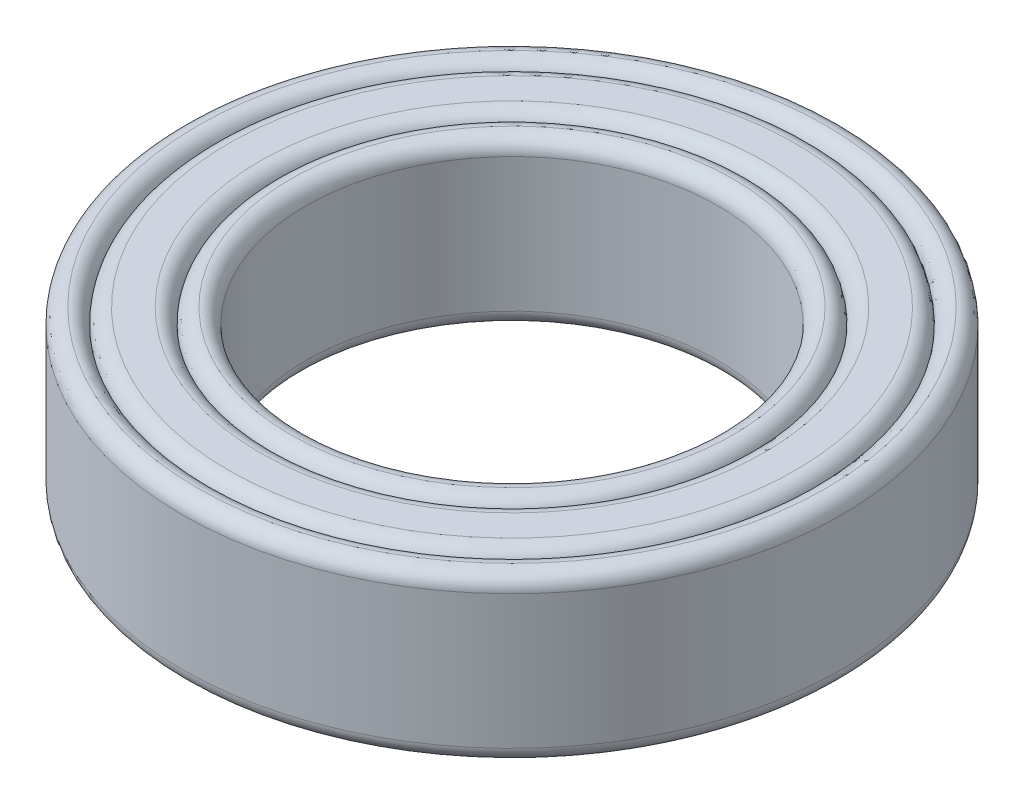
SolidWorks part; units mm, degrees
ref_plane "Front Plane" through (0, 0, 0) normal (0, 0, 1) x (1, 0, 0)
ref_plane "Top Plane" through (0, 0, 0) normal (0, 1, 0) x (1, 0, 0)
ref_plane "Right Plane" through (0, 0, 0) normal (1, 0, 0) x (0, 0, -1)
sketch "Sketch1" plane through (0, 0, 0) normal (0, 1, 0) x (1, 0, 0)
  circle A0 centre (0, 0) radius 8
  dimension "D1" = 16
extrude "Boss-Extrude1" add sketch "Sketch1" along normal mid plane 4
fillet "Fillet1" radius 0.375 2 edges at (0, -2, 8) (0, 2, 8)
sketch "Sketch2" plane through (0, 0, 0) normal (0, 1, 0) x (1, 0, 0)
  circle A0 centre (0, 0) radius 7.25
  dimension "D1" = 14.5
extrude "Cut-Extrude1" cut sketch "Sketch2" against normal through all both and the other way through all
fillet "Fillet2" radius 0.375 2 edges at (0, 2, 7.25) (0, -2, 7.25)
sketch "Sketch3" plane through (0, 0, 0) normal (0, 1, 0) x (1, 0, 0)
  circle A0 centre (0, 0) radius 7.25
  dimension "D1" = 14.5
extrude "Boss-Extrude2" add sketch "Sketch3" along normal through all and the other way through all
fillet "Fillet3" radius 0.375 2 edges at (0, -2, 7.25) (0, 2, 7.25)
sketch "Sketch4" plane through (0, 0, 0) normal (0, 1, 0) x (1, 0, 0)
  circle A0 centre (0, 0) radius 5.75
  dimension "D1" = 11.5
extrude "Cut-Extrude2" cut sketch "Sketch4" against normal through all both and the other way through all
fillet "Fillet4" radius 0.375 2 edges at (0, 2, 5.75) (0, -2, 5.75)
sketch "Sketch5" plane through (0, 0, 0) normal (0, 1, 0) x (1, 0, 0)
  circle A0 centre (0, 0) radius 5.75
  dimension "D1" = 11.5
extrude "Boss-Extrude3" add sketch "Sketch5" along normal through all and the other way through all
fillet "Fillet5" radius 0.375 2 edges at (0, -2, 5.75) (0, 2, 5.75)
sketch "Sketch6" plane through (0, 0, 0) normal (0, 1, 0) x (1, 0, 0)
  circle A0 centre (0, 0) radius 5
  dimension "D1" = 10
extrude "Cut-Extrude3" cut sketch "Sketch6" against normal through all both and the other way through all
fillet "Fillet6" radius 0.375 2 edges at (0, 2, 5) (0, -2, 5)
equation "\"D1@Boss-Extrude1\" = \"ARM Both Nema Bearing Thickness\""
equation "\"D1@Sketch1\" = \"ARM Both Nema Bearing OD\""
equation "\"D1@Fillet1\" = \"ALL Small Fillet\" * ( 3 / 4 )"
equation "\"D1@Fillet2\" = \"ALL Small Fillet\" * ( 3 / 4 )"
equation "\"D1@Fillet3\" = \"ALL Small Fillet\" * ( 3 / 4 )"
equation "\"D1@Fillet4\" = \"ALL Small Fillet\" * ( 3 / 4 )"
equation "\"D1@Fillet5\" = \"ALL Small Fillet\" * ( 3 / 4 )"
equation "\"D1@Fillet6\"= \"ALL Small Fillet\" * ( 3 / 4 )"
equation "\"D1@Sketch2\" = \"ARM Both Nema Bearing OD\" - ( ( \"ARM Both Nema Bearing OD\" - \"ARM Both Nema Bearing ID\" ) / 4 )"
equation "\"D1@Sketch6\" = \"ARM Both Nema Bearing ID\""
equation "\"D1@Sketch4\" = \"ARM Both Nema Bearing ID\" + ( ( \"ARM Both Nema Bearing OD\" - \"ARM Both Nema Bearing ID\" ) / 4 )"
equation "\"D1@Sketch3\" = \"ARM Both Nema Bearing OD\" - ( ( \"ARM Both Nema Bearing OD\" - \"ARM Both Nema Bearing ID\" ) / 4 )"
equation "\"D1@Sketch5\" = \"ARM Both Nema Bearing ID\" + ( ( \"ARM Both Nema Bearing OD\" - \"ARM Both Nema Bearing ID\" ) / 4 )"
equation "\"ALL Big Fillet\"= 10.0mm"
equation "\"ALL Medium Fillet\"= 1.0mm"
equation "\"ALL Small Fillet\"= 0.5mm"
equation "\"BODY Rad\"= 82.5mm"
equation "\"BODY End Cut Rad\"= 72.5mm"
equation "\"BODY Height Ext\"= 27.5mm"
equation "\"BODY Bottom Cut Dist\"= 50.0mm"
equation "\"BODY Seal Thickness\"= 3.75mm"
equation "\"BODY Wall Extra Thickness\"= 2.5mm"
equation "\"BODY Bottom Extra Nut Wall\"= 7.5mm"
equation "\"ARM Both Dia\"= 39.75mm"
equation "\"ARM Both Length\"= 67.5mm"
equation "\"ARM Both Wire Hole Dia\"= 15.0mm"
equation "\"ARM Both Prop Seal Thickness\"= 2.5mm"
equation "\"ARM Both Brass Insert Dia\"= 4.875mm"
equation "\"ARM Both Bolt Cut Depth\"= 12.5mm"
equation "\"ARM Both Nema Bolt Off\"= 15.4mm"
equation "\"ARM Both Nema Bolt Depth\"= 2.5mm"
equation "\"ARM Both Nema Width\"= 20.0mm"
equation "\"ARM Both Nema Wall Off\"= 2.5mm"
equation "\"ARM Both Nema Center Dia 1\"= 17.0mm"
equation "\"ARM Both Nema Center Dia 2\"= 10.0mm"
equation "\"ARM Both Nema Bearing OD\"= 16.0mm"
equation "\"ARM Both Nema Bearing ID\"= 10.0mm"
equation "\"ARM Both Nema Bearing Thickness\"= 4.0mm"
equation "\"ARM Both Nema Height\"= 38.0mm"
equation "\"ARM Both Nema Shaft Dia\"= 4.0mm"
equation "\"ARM Both Nema Shaft Length\"= 10.0mm"
equation "\"ARM Both Nema Center Height\"= 1.5mm"
equation "\"ARM Rotating Bearing OD\"= 68.0mm"
equation "\"ARM Rotating Bearing ID\"= 40.0mm"
equation "\"ARM Rotating Bearing Thickness\"= 15.0mm"
equation "\"ARM Static Mount Dia\"= 65.0mm"
equation "\"ARM Static Bolt Off\"= 1.125mm"
equation "\"ALL Bolt Hole Off\"= 0.25mm"
equation "\"ALL Vert Bolt Hole Off Scalar\"= 0.5mm"
equation "\"ALL Horz Bolt Hole Off Scalar\"= 1.25mm"
equation "\"ALL Nut Size Off\"= 0.25mm"
equation "\"ALL Vert Nut Off Scalar\"= 0.5mm"
equation "\"ALL Horz Nut Off Scalar\"= 1.25mm"
equation "\"BODY Bolt Count\"= 12"
equation "\"BODY Bolt Size\"= 6"
equation "\"BODY Bolt Length\"= 22.0mm"
equation "\"BODY Bolt Head Dia\"= IIF ( \"BODY Bolt Size\" = 3 , 5.75mm , IIF ( \"BODY Bolt Size\" = 4 , 7.25mm , IIF ( \"BODY Bolt Size\" = 5 , 8.75mm , IIF ( \"BODY Bolt Size\" = 6 , 10.25mm , 5.75mm ) ) ) )"
equation "\"BODY Bolt Head Height\"= IIF ( \"BODY Bolt Size\" = 3 , 3.0mm , IIF ( \"BODY Bolt Size\" = 4 , 4.0mm , IIF ( \"BODY Bolt Size\" = 5 , 5.0mm , IIF ( \"BODY Bolt Size\" = 6 , 6.0mm , 3.0mm ) ) ) )"
equation "\"BODY Nut Width\"= IIF ( \"BODY Bolt Size\" = 3 , 5.5mm , IIF ( \"BODY Bolt Size\" = 4 , 7.0mm , IIF ( \"BODY Bolt Size\" = 5 , 8.0mm , IIF ( \"BODY Bolt Size\" = 6 , 10.0mm , 5.5mm ) ) ) )"
equation "\"BODY Nut Height\"= IIF ( \"BODY Bolt Size\" = 3 , 4.0mm , IIF ( \"BODY Bolt Size\" = 4 , 5.0mm , IIF ( \"BODY Bolt Size\" = 5 , 5.0mm , IIF ( \"BODY Bolt Size\" = 6 , 6.0mm , 4.0mm ) ) ) )"
equation "\"ARM Static Bolt Count\"= 8"
equation "\"ARM Static Bolt Size\"= 5"
equation "\"ARM Static Bolt Length\"= 20.0mm"
equation "\"ARM Static Bolt Head Dia\"= IIF ( \"ARM Static Bolt Size\" = 3 , 5.75mm , IIF ( \"ARM Static Bolt Size\" = 4 , 7.25mm , IIF ( \"ARM Static Bolt Size\" = 5 , 8.75mm , IIF ( \"ARM Static Bolt Size\" = 6 , 10.25mm , 5.75mm ) ) ) )"
equation "\"ARM Static Bolt Head Height\"= IIF ( \"ARM Static Bolt Size\" = 3 , 3.0mm , IIF ( \"ARM Static Bolt Size\" = 4 , 4.0mm , IIF ( \"ARM Static Bolt Size\" = 5 , 5.0mm , IIF ( \"ARM Static Bolt Size\" = 6 , 6.0mm , 3.0mm ) ) ) )"
equation "\"ARM Static Nut Width\"= IIF ( \"ARM Static Bolt Size\" = 3 , 5.5mm , IIF ( \"ARM Static Bolt Size\" = 4 , 7.0mm , IIF ( \"ARM Static Bolt Size\" = 5 , 8.0mm , IIF ( \"ARM Static Bolt Size\" = 6 , 10.0mm , 5.5mm ) ) ) )"
equation "\"ARM Static Nut Height\"= IIF ( \"ARM Static Bolt Size\" = 3 , 4.0mm , IIF ( \"ARM Static Bolt Size\" = 4 , 5.0mm , IIF ( \"ARM Static Bolt Size\" = 5 , 5.0mm , IIF ( \"ARM Static Bolt Size\" = 6 , 6.0mm , 4.0mm ) ) ) )"
equation "\"ARM Gear Width\"= 10.0mm"
equation "\"ARM Gear Width Off\"= 2.5mm"
equation "\"ARM Gear Bolt Count\"= 4"
equation "\"ARM Gear Rotation\"= 360.0deg"
equation "\"ARM Gear Bolt Size\"= 3"
equation "\"ARM Gear Bolt Length\"= 20.0mm"
equation "\"ARM Gear Bolt Head Dia\"= IIF ( \"ARM Static Bolt Size\" = 3 , 5.75mm , IIF ( \"ARM Static Bolt Size\" = 4 , 7.25mm , IIF ( \"ARM Static Bolt Size\" = 5 , 8.75mm , IIF ( \"ARM Static Bolt Size\" = 6 , 10.25mm , 5.75mm ) ) ) )"
equation "\"ARM Gear Bolt Head Height\"= IIF ( \"ARM Static Bolt Size\" = 3 , 3.0mm , IIF ( \"ARM Static Bolt Size\" = 4 , 4.0mm , IIF ( \"ARM Static Bolt Size\" = 5 , 5.0mm , IIF ( \"ARM Static Bolt Size\" = 6 , 6.0mm , 3.0mm ) ) ) )"
equation "\"ARM Gear Nut Width\"= IIF ( \"ARM Static Bolt Size\" = 3 , 5.5mm , IIF ( \"ARM Static Bolt Size\" = 4 , 7.0mm , IIF ( \"ARM Static Bolt Size\" = 5 , 8.0mm , IIF ( \"ARM Static Bolt Size\" = 6 , 10.0mm , 5.5mm ) ) ) )"
equation "\"ARM Gear Nut Height\"= IIF ( \"ARM Static Bolt Size\" = 3 , 4.0mm , IIF ( \"ARM Static Bolt Size\" = 4 , 5.0mm , IIF ( \"ARM Static Bolt Size\" = 5 , 5.0mm , IIF ( \"ARM Static Bolt Size\" = 6 , 6.0mm , 4.0mm ) ) ) )"
equation "\"ARM Both Prop Plate Bolt Size\"= 3"
equation "\"ARM Both Prop Plate Bolt Length\"= 16.0mm"
equation "\"ARM Both Prop Plate Bolt Head Dia\"= IIF ( \"ARM Both Prop Plate Bolt Size\" = 3 , 5.75mm , IIF ( \"ARM Both Prop Plate Bolt Size\" = 4 , 7.25mm , IIF ( \"ARM Both Prop Plate Bolt Size\" = 5 , 8.75mm , IIF ( \"ARM Both Prop Plate Bolt Size\" = 6 , 10.25mm , 5.75mm ) ) ) )"
equation "\"ARM Both Prop Plate Bolt Head Height\"= IIF ( \"ARM Both Prop Plate Bolt Size\" = 3 , 3.0mm , IIF ( \"ARM Both Prop Plate Bolt Size\" = 4 , 4.0mm , IIF ( \"ARM Both Prop Plate Bolt Size\" = 5 , 5.0mm , IIF ( \"ARM Both Prop Plate Bolt Size\" = 6 , 6.0mm , 3.0mm ) ) ) )"
equation "\"ARM Both Nema Bolt Size\"= 2"
equation "\"ARM Both Nema Bolt Head Dia\"= IIF ( \"ARM Both Nema Bolt Size\" = 3 , 5.75mm , IIF ( \"ARM Both Nema Bolt Size\" = 4 , 7.25mm , IIF ( \"ARM Both Nema Bolt Size\" = 5 , 8.75mm , IIF ( \"ARM Both Nema Bolt Size\" = 6 , 10.25mm , 5.75mm ) ) ) )"
equation "\"ARM Both Nema Bolt Head Height\"= IIF ( \"ARM Both Nema Bolt Size\" = 3 , 3.0mm , IIF ( \"ARM Both Nema Bolt Size\" = 4 , 4.0mm , IIF ( \"ARM Both Nema Bolt Size\" = 5 , 5.0mm , IIF ( \"ARM Both Nema Bolt Size\" = 6 , 6.0mm , 3.0mm ) ) ) )"
